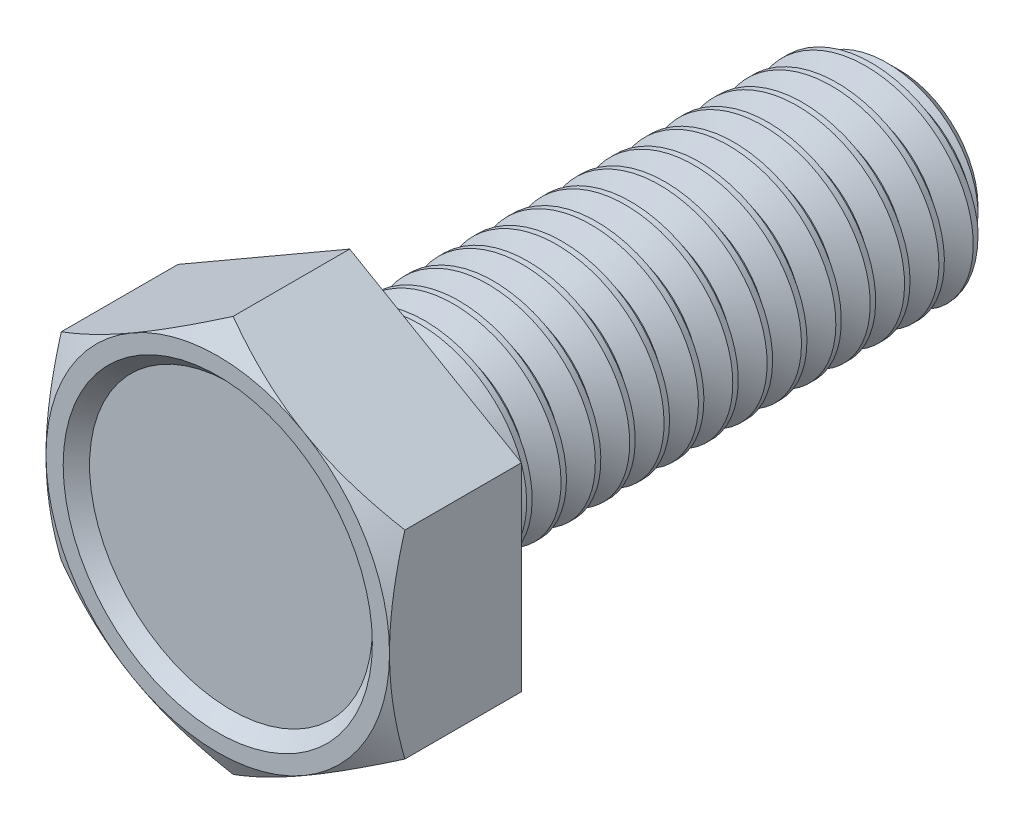
SolidWorks part; units mm, degrees
material "Plain Carbon Steel"
ref_plane "Front" through (0, 0, 0) normal (0, 0, 1) x (1, 0, 0)
ref_plane "Top" through (0, 0, 0) normal (0, 1, 0) x (1, 0, 0)
ref_plane "Right" through (0, 0, 0) normal (1, 0, 0) x (0, 0, -1)
sketch "Sketch1" plane through (0, 0, 0) normal (0, 0, 1) x (1, 0, 0)
  line L1 (-3.9688, -2.2914) -> (0, -4.5827)
  line L2 (0, -4.5827) -> (3.9688, -2.2914)
  line L3 (3.9688, -2.2914) -> (3.9687, 2.2914)
  line L4 (3.9687, 2.2914) -> (0, 4.5827)
  line L5 (0, 4.5827) -> (-3.9688, 2.2914)
  line L6 (-3.9688, 2.2914) -> (-3.9688, -2.2914)
  circle A0 centre (0, 0) radius 3.9688 construction
  circle A1 centre (0, 0) radius 3.9688 construction
  dimension "Head Dia" = 7.9375
extrude "Extrude3" add sketch "Sketch1" along normal blind 3.048
sketch "Sketch4" plane through (0, 0, 0) normal (1, 0, 0) x (0, 0, -1)
  line L0 (0, 0) -> (12.7, 0)
  line L3 (12.7, 0) -> (12.7, 2.413)
  line L4 (12.7, 2.413) -> (0, 2.413)
  line L6 (0, 2.413) -> (0, 0)
  line L9 (12.7, 2.413) -> (12.7, -2.413) construction
  dimension "length" = 12.7
  dimension "dia" = 4.826
revolve "Revolve1" add sketch "Sketch4" angle 360 about L0
sketch "Sketch13" plane through (0, 0, -12.7) normal (0, 0, -1) x (-1, 0, 0)
  circle A2 centre (0, 0) radius 2.413
curve "Helix/Spiral1" pitch 0.7937 height 15.748 radius 2.413 centre (0, 0, -12.7) axis (0, 0, 1) start towards (1, 0, 0)
chamfer "Chamfer2" distance 0.5953 angle 45 1 edges at (2.413, 0, -12.7)
sketch "Sketch14" plane through (0, 0, 0) normal (1, 0, 0) x (0, 0, -1)
  line L0 (12.7, 2.4378) -> (13.3945, 2.4378)
  line L1 (13.3945, 2.4378) -> (13.0969, 1.9008)
  line L2 (13.0969, 1.9008) -> (12.9977, 1.9008)
  line L3 (12.9977, 1.9008) -> (12.7, 2.4378)
  line L4 (12.8488, 2.1693) -> (13.2457, 2.1693) construction
  dimension "D1" = 0.0992
  dimension "D2" = 58
  dimension "D3" = 0.3969
  dimension "D4" = 0.0248
sweep "Cut-Sweep1" cut profiles "Sketch14" path "Helix/Spiral1" align with end faces yes
ref_plane "Plane1" through (0, 0, 25.4) normal (0, 0, -1) x (-1, 0, 0)
sketch "Sketch29" [suppressed] plane through (0, 0, 28.575) normal (0, 0, -1) x (-1, 0, 0)
  circle A0 centre (0, 0) radius 1.7526 construction
  circle A1 centre (0, 0) radius 1.7526
  point P3 (0, -1.7526)
  point P4 (0, 1.7526)
extrude "Extrude11" [suppressed] add sketch "Sketch29" against normal up to surface (28.575 mm away) up to plane "Front"
sketch "Sketch26" plane through (0, 0, 0) normal (0, 0, 1) x (1, 0, 0)
  circle A1 centre (0, 0) radius 0.5461
  dimension "D1" = 1.0922
extrude "Extrude12" add sketch "Sketch26" along normal up to surface (3.048 mm away) up to face at (0, 0, 3.048)
sketch "Sketch30" plane through (0, 0, 3.048) normal (0, 0, 1) x (1, 0, 0)
  circle A0 centre (0, 0) radius 3.9688 construction
  circle A1 centre (0, 0) radius 3.9688
extrude "Extrude13" cut sketch "Sketch30" against normal blind 2.54 draft 60 flip side to cut
sketch "Sketch31" plane through (0, 0, 3.048) normal (0, 0, 1) x (1, 0, 0)
  circle A0 centre (0, 0) radius 3.5719
  dimension "D1" = 7.1437
extrude "Extrude14" cut sketch "Sketch31" against normal blind 0.3048 draft 45
sketch "Sketch18" plane through (0, 0, 0) normal (1, 0, 0) x (0, 0, -1)
  line L1 (12.7, 2.413) -> (0, 2.413) construction
  line L2 (-3.048, 3.9688) -> (-3.048, 3.437) construction
  point P0 (11.5094, -2.413)
  point P1 (11.9062, 2.413)
  point P2 (-3.048, 4.5827)
  dimension "D1" = 0.7937
  dimension "D2" = 1.1906
equation "\"D3@Helix/Spiral1\" = \"length@Sketch4\" + \"Head Ht@Extrude3\""
equation "\"D1@Sketch14\" = \"D4@Helix/Spiral1\" * .125"
equation "\"D3@Sketch14\" = \"D4@Helix/Spiral1\" * .5"
equation "\"D4@Sketch14\" = \"D1@Sketch14\" * .25"
equation "\"D1@Chamfer2\" = \"D4@Helix/Spiral1\" * .75"
equation "\"D1@Sketch18\" = \"D4@Helix/Spiral1\""
equation "\"D2@Sketch18\" = \"D4@Helix/Spiral1\" * 1.5"
equation "\"D1@Sketch31\" = \"Head Dia@Sketch1\" * .9"
equation "\"D1@Extrude14\" = \"Head Ht@Extrude3\" * .1"
